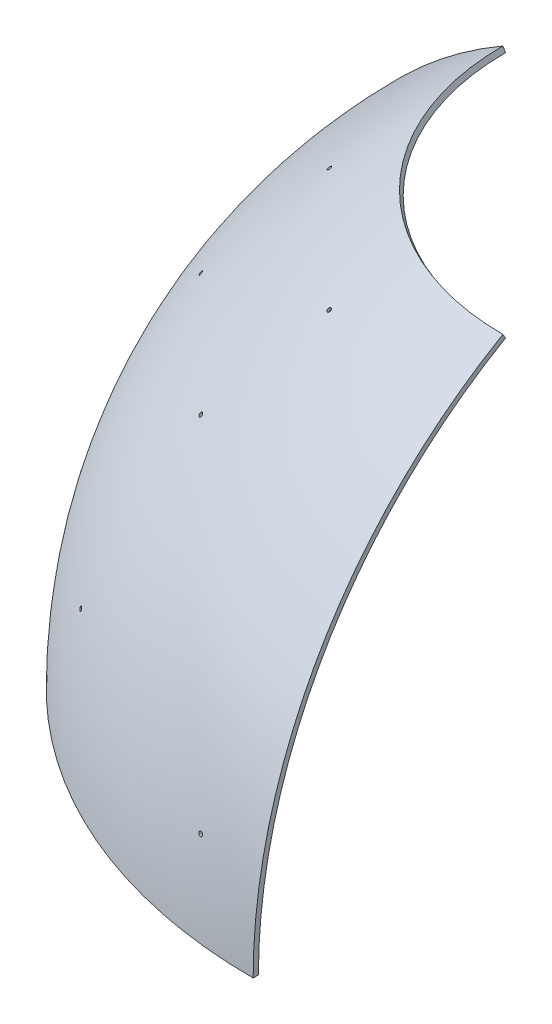
SolidWorks part; units mm, degrees
ref_plane "Front" through (0, 0, 0) normal (0, 0, 1) x (1, 0, 0)
ref_plane "Top" through (0, 0, 0) normal (0, 1, 0) x (1, 0, 0)
ref_plane "Right" through (0, 0, 0) normal (1, 0, 0) x (0, 0, -1)
sketch "Sketch1" plane through (0, 0, 0) normal (0, 0, 1) x (1, 0, 0)
  line L0 (0, 0) -> (-322.049, 0)
  line L1 (0, 0) -> (0, 286.8634)
  line L2 (0, 0) -> (-137.1535, 237.5569)
  circle A0 centre (0, 0) radius 237.5
  circle A1 centre (0, 0) radius 235
  circle A2 centre (0, 0) radius 236.25
  dimension "D1" = 475
  dimension "D2" = 470
  dimension "D3" = 472.5
  dimension "D4" = 30
revolve "Revolve1" add sketch "Sketch1" angle 90 about L1 region at (-235.625, 2.3656, 0) region at (-236.875, 2.3781, 0)
sketch "Sketch2" plane through (0, 0, 0) normal (0, 0, 1) x (1, 0, 0)
  line L0 (0, 0) -> (0, 145.8567)
ref_plane "Plane1" through (0, 0, 0) normal (0.9914, 0, 0.1305) x (0, 1, 0)
sketch "Sketch3" plane through (0, 0, 0) normal (0.9914, 0, 0.1305) x (0, 1, 0)
  line L0 (0, 0) -> (49.8683, 282.8172)
  line L1 (0, 0) -> (0, 278.9678)
  line L2 (0.9848, -0.1736) -> (50.8531, 282.6436)
  line L3 (2.9544, -0.5209) -> (52.8227, 282.2963)
  circle A0 centre (0, 0) radius 236.25
  circle A1 centre (0, 0) radius 235
  circle A2 centre (0, 0) radius 237.5
  dimension "D3" = 472.5
  dimension "D4" = 470
  dimension "D5" = 475
  dimension "D1" = 10
  dimension "D2" = 1
  dimension "D6" = 3
revolve "Cut-Revolve1" cut sketch "Sketch3" angle 360 about L0 region at (-30.2766, 41.4081, 229.9734) region at (-30.4372, 41.6252, 231.1939) region at (-30.2415, 42.8839, 229.7068)
ref_plane "Plane2" through (0, 0, 0) normal (0.7071, 0, 0.7071) x (0, 1, 0)
sketch "Sketch4" plane through (0, 0, 0) normal (0, 1, 0) x (1, 0, 0)
  line L0 (0, 0) -> (-283.4977, 0)
  line L1 (0, 0) -> (-238.1017, -238.1017)
  dimension "D1" = 45
ref_plane "Plane3" through (0, 0, 0) normal (0, 0.7071, -0.7071) x (-1, 0, 0)
ref_axis "Axis1" through (34.9327, -34.9327, -34.9327) along (-0.5774, 0.5774, 0.5774)
ref_plane "Plane4" through (0, 0, 0) normal (-0.5, 0.7071, -0.5) x (-0.7071, 0, 0.7071)
mirror "Mirror2" about plane through (0, 0, 0) normal (-0.5, 0.7071, -0.5) of "Cut-Revolve1"
ref_axis "Axis3" through (0, -50, -70.7107) along (0, 0.5774, 0.8165)
pattern_circular "CirPattern3" count 2 every 120 about axis through (0, -50, -70.7107) along (0, 0.5774, 0.8165) of "Cut-Revolve1" reverse direction yes
mirror "Mirror5" about plane through (0, 0, 0) normal (0.7071, 0, 0.7071) of "Mirror2", "CirPattern3", "Cut-Revolve1"
ref_plane "Plane6" through (0, 0, 0) normal (0.8192, 0, 0.5736) x (0, 1, 0)
sketch "Sketch7" plane through (0, 0, 0) normal (0.8192, 0, 0.5736) x (0, 1, 0)
  line L0 (0, 0) -> (73.1392, 272.9592)
  line L1 (0, 0) -> (0, 268.8522)
  line L2 (2.8978, -0.7765) -> (76.037, 272.1828)
  line L3 (0.9659, -0.2588) -> (74.1051, 272.7004)
  circle A0 centre (0, 0) radius 237.5
  circle A1 centre (0, 0) radius 235
  circle A2 centre (0, 0) radius 236.25
  dimension "D4" = 475
  dimension "D5" = 470
  dimension "D6" = 472.5
  dimension "D1" = 15
  dimension "D2" = 3
  dimension "D3" = 1
revolve "Cut-Revolve2" cut sketch "Sketch7" angle 360 about L0 region at (-130.4692, 61.467, 186.3294) region at (-131.1618, 61.7905, 187.3184) region at (-130.2419, 62.9137, 186.0046)
mirror "Mirror6" about plane through (0, 0, 0) normal (0.7071, 0, 0.7071) of "Cut-Revolve2"
